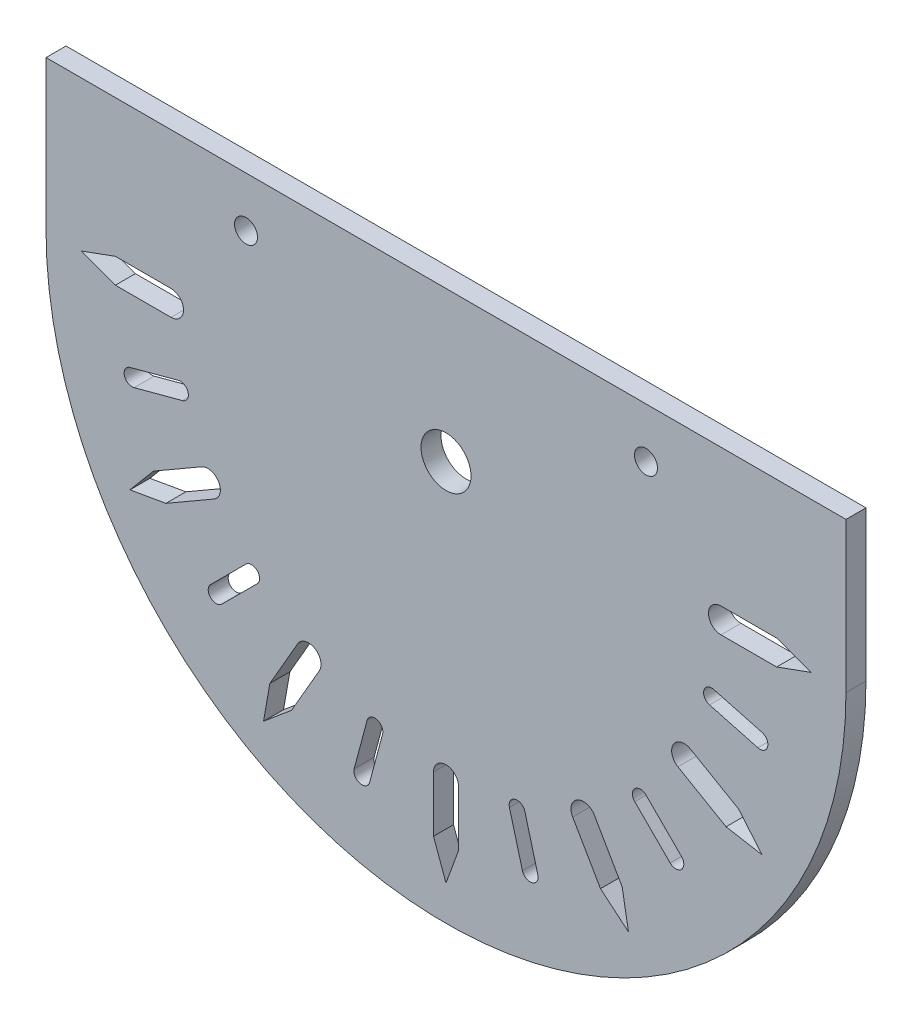
SolidWorks part; units mm, degrees
note: '?' marks a value the reader was unsure of.
ref_plane "Front Plane" through (0, 0, 0) normal (0, 0, 1) x (1, 0, 0)
ref_plane "Top Plane" through (0, 0, 0) normal (0, 1, 0) x (1, 0, 0)
ref_plane "Right Plane" through (0, 0, 0) normal (1, 0, 0) x (0, 0, -1)
sketch "Sketch1" plane through (0, 0, 0) normal (0, 0, 1) x (1, 0, 0)
  line L0 (-40, 0) -> (40, 0) construction
  line L1 (-40, 0) -> (-40, 15)
  line L2 (-40, 15) -> (40, 15)
  line L3 (40, 15) -> (40, 0)
  line L4 (0, 0) -> (-34.641, -20) construction
  line L5 (0, 0) -> (0, -40) construction
  line L6 (0, 0) -> (34.641, -20) construction
  line L7 (0, 0) -> (-28.2843, -28.2843) construction
  line L8 (0, 0) -> (28.2843, -28.2843) construction
  line L9 (0, 0) -> (20, -34.641) construction
  line L10 (0, 0) -> (-20, -34.641) construction
  line L11 (-33.0657, 0) -> (-27.5, 0) construction
  line L12 (-33.0657, 1.25) -> (-27.5, 1.25)
  line L13 (-33.0657, -1.25) -> (-27.5, -1.25)
  line L14 (0, 0) -> (-38.637, -10.3528) construction
  line L17 (-36.5, 0) -> (-33.0657, 1.25)
  line L18 (-36.5, 0) -> (-33.0657, -1.25)
  arc A0 (40, 0) -> (-40, 0) centre (0, 0) cw
  arc A2 (-27.5, -1.25) -> (-27.5, 1.25) centre (-27.5, 0) ccw
  circle A5 centre (0, 0) radius 27.5 construction
  circle A6 centre (0, 0) radius 25 construction
  point P4 (0, 0)
  dimension "D9" = 55
  dimension "D10" = 1.25
  dimension "D11" = 9
  dimension "D15" = 50
  dimension "D1" = 80
  dimension "D2" = 15
  dimension "D3" = 30
  dimension "D4" = 30
  dimension "D5" = 45
  dimension "D6" = 45
  dimension "D7" = 60
  dimension "D8" = 60
  dimension "D12" = 20
  dimension "D13" = 2.5
  dimension "D14" = 15
extrude "Boss-Extrude1" add sketch "Sketch1" along normal blind 2 contours A0 L3 L2 L1 A2 L13 L18 L17 L12 | L13 A2 L12 L17 L18
sketch "Sketch2" plane through (0, 0, 2) normal (0, 0, 1) x (1, 0, 0)
  line L0 (-36.5, 0) -> (-33.0657, -1.25) construction
  line L1 (-33.0657, -1.25) -> (-27.5, -1.25) construction
  line L2 (-33.0657, 1.25) -> (-27.5, 1.25) construction
  line L3 (40, 0) -> (40, 15)
  line L4 (40, 15) -> (-40, 15)
  line L5 (-40, 15) -> (-40, 0)
  line L6 (40, 0) -> (40, 15)
  line L7 (40, 15) -> (-40, 15)
  line L8 (-40, 15) -> (-40, 0)
  line L9 (-36.5, 0) -> (-33.0657, 1.25) construction
  line L10 (-36.5, 0) -> (-33.0657, -1.25)
  line L11 (-33.0657, -1.25) -> (-27.5, -1.25)
  line L12 (-33.0657, 1.25) -> (-27.5, 1.25)
  line L13 (-36.5, 0) -> (-33.0657, 1.25)
  arc A0 (-27.5, -1.25) -> (-27.5, 1.25) centre (-27.5, 0) ccw construction
  arc A1 (-40, 0) -> (40, 0) centre (0, 0) ccw
  arc A2 (-40, 0) -> (40, 0) centre (0, 0) ccw
  arc A3 (-27.5, -1.25) -> (-27.5, 1.25) centre (-27.5, 0) ccw
  dimension "D1" = 0
extrude "Cut-Extrude2" cut sketch "Sketch2" against normal up to surface (2 mm away) contours L11 A3 L12 L13 L10 up to face at (0, -2.5, 0)
ref_axis "Axis1" through (0, 0, 0) along (0, 0, 1)?
pattern_circular "CirPattern1" count 7 every 30 about axis through (0, 0, 0) along (0, 0, 1) of "Cut-Extrude2"
sketch "Sketch4" plane through (0, 0, 2) normal (0, 0, 1) x (1, 0, 0)
  line L0 (-40, 0) -> (40, 0) construction
  line L1 (-26.563, -7.1175) -> (-31.3926, -8.4116) construction
  line L2 (-26.3559, -7.8903) -> (-31.1855, -9.1844)
  line L3 (-26.77, -6.3448) -> (-31.5996, -7.6389)
  line L4 (-26.77, -6.3448) -> (-26.3559, -7.8903) construction
  line L6 (0, 0) -> (-38.637, -10.3528) construction
  circle A0 centre (0, 0) radius 27.5 construction
  arc A1 (-26.3559, -7.8903) -> (-26.77, -6.3448) centre (-26.563, -7.1175) ccw
  arc A2 (-31.5996, -7.6389) -> (-31.1855, -9.1844) centre (-31.3926, -8.4116) ccw
  point P4 (-28.9778, -7.7646)
  dimension "D1" = 0.8
  dimension "45" = 55
  dimension "D2" = 5
extrude "Cut-Extrude3" cut sketch "Sketch4" against normal up to surface (2 mm away) up to face at (-27.086, -15.6381, 0)
pattern_circular "CirPattern2" count 6 every 30 about axis through (0, 0, 0) along (0, 0, 1) of "Cut-Extrude3"
sketch "Sketch5" plane through (0, 0, 2) normal (0, 0, 1) x (1, 0, 0)
  line L0 (-40, 0) -> (40, 0) construction
  circle A0 centre (0, 0) radius 2.5
  dimension "D1" = 5
extrude "Cut-Extrude4" cut sketch "Sketch5" against normal up to surface (2 mm away) up to face at (-21.2132, -21.2132, 0)
sketch "Sketch6" plane through (0, 0, 2) normal (0, 0, 1) x (1, 0, 0)
  line L0 (-50.8735, 0) -> (50.8735, 0) construction
  line L1 (0, 17.1975) -> (0, -10.7531) construction
  circle A0 centre (-20, 10) radius 1.15
  circle A1 centre (20, 10) radius 1.15
  point P5 (0, 0)
  dimension "D3" = 2.3
  dimension "D1" = 20
  dimension "D2" = 10
extrude "Cut-Extrude5" cut sketch "Sketch6" against normal up to surface (2 mm away) up to face at (2.5, 0, 0)
sketch "Sketch7" plane through (0, 0, 2) normal (0, 0, 1) x (1, 0, 0)
  line L0 (-26.25, 0) -> (-4.25, 0) construction
  line L2 (-26.25, 0.5) -> (-4.25, 0.5)
  line L3 (-26.25, -0.5) -> (-4.25, -0.5)
  line L4 (-40, 0) -> (40, 0) construction
  arc A0 (-27.5, -1.25) -> (-27.5, 1.25) centre (-27.5, 0) ccw construction
  arc A2 (-26.25, 0.5) -> (-26.25, -0.5) centre (-26.25, 0) ccw
  arc A3 (-4.25, -0.5) -> (-4.25, 0.5) centre (-4.25, 0) ccw
  point P9 (-15.25, 0)
  dimension "D1" = 1
  dimension "D2" = 22
extrude "Cut-Extrude6" [suppressed] cut sketch "Sketch7" against normal blind 10
pattern_circular "CirPattern3" [suppressed] count 7 every 30 about axis through (0, 0, 0) along (0, 0, 1)
